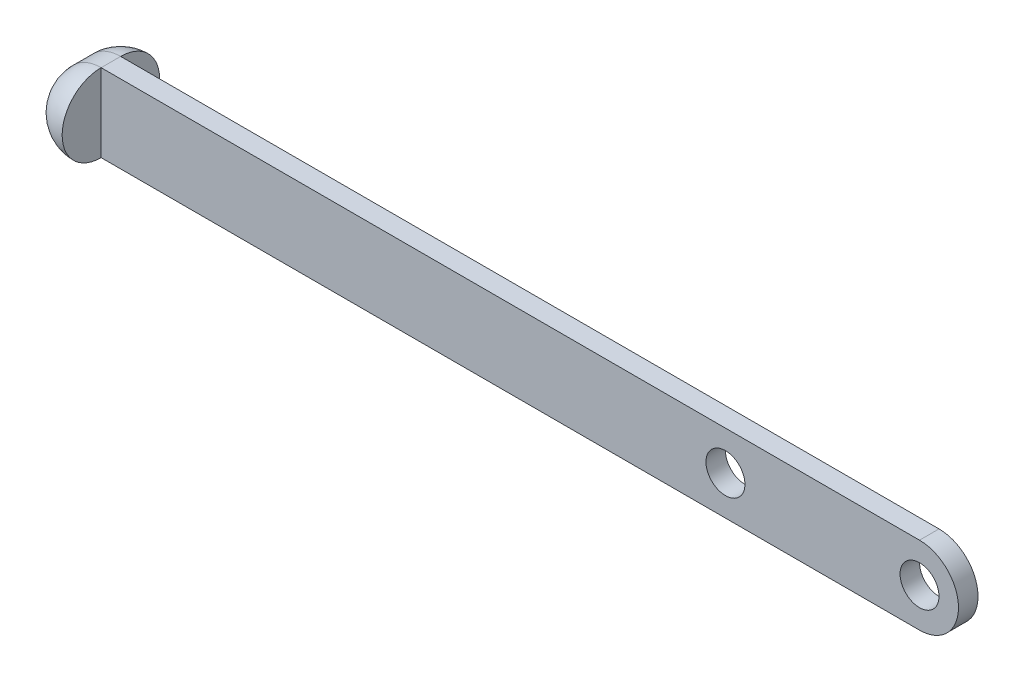
SolidWorks part; units mm, degrees
ref_plane "Front Plane" through (0, 0, 0) normal (0, 0, 1) x (1, 0, 0)
ref_plane "Top Plane" through (0, 0, 0) normal (0, 1, 0) x (1, 0, 0)
ref_plane "Right Plane" through (0, 0, 0) normal (1, 0, 0) x (0, 0, -1)
sketch "Sketch1" plane through (0, 0, 0) normal (0, 0, 1) x (1, 0, 0)
  line L0 (-54.3874, 0) -> (50.4828, 0) construction
  line L1 (-54.3874, 4.9938) -> (50.4828, 4.9938)
  line L2 (-54.3874, -4.9938) -> (50.4828, -4.9938)
  arc A0 (-54.3874, 4.9938) -> (-54.3874, -4.9938) centre (-54.3874, 0) ccw
  arc A1 (50.4828, -4.9938) -> (50.4828, 4.9938) centre (50.4828, 0) ccw
  circle A3 centre (50.4828, 0) radius 2.4969
  circle A4 centre (25.6126, 0) radius 2.4969
  point P3 (-1.9523, 0)
  dimension "D1" = 80
extrude "Boss-Extrude1" add sketch "Sketch1" along normal blind 2.5
sketch "Sketch2" plane through (0, 0, 2.5) normal (0, 0, 1) x (1, 0, 0)
  line L0 (-54.3874, 5) -> (-54.3874, -4.9938) construction
  line L1 (-54.3874, 5) -> (-54.3874, -4.9938)
  arc A2 (-54.3874, -4.9938) -> (-54.3874, 5) centre (-54.3874, 0.0031) cw
revolve "Revolve1" add sketch "Sketch2" angle 90 about L0 reverse direction yes
sketch "Sketch3" plane through (0, 0, 0) normal (0, 0, -1) x (-1, 0, 0)
  line L0 (54.3874, 4.9938) -> (54.3874, -4.9938) construction
  line L1 (54.3874, 4.9938) -> (54.3874, -4.9938)
  arc A0 (54.3874, 4.9938) -> (54.3874, -4.9938) centre (54.3874, 0) cw
revolve "Revolve2" add sketch "Sketch3" angle 90 about L0
